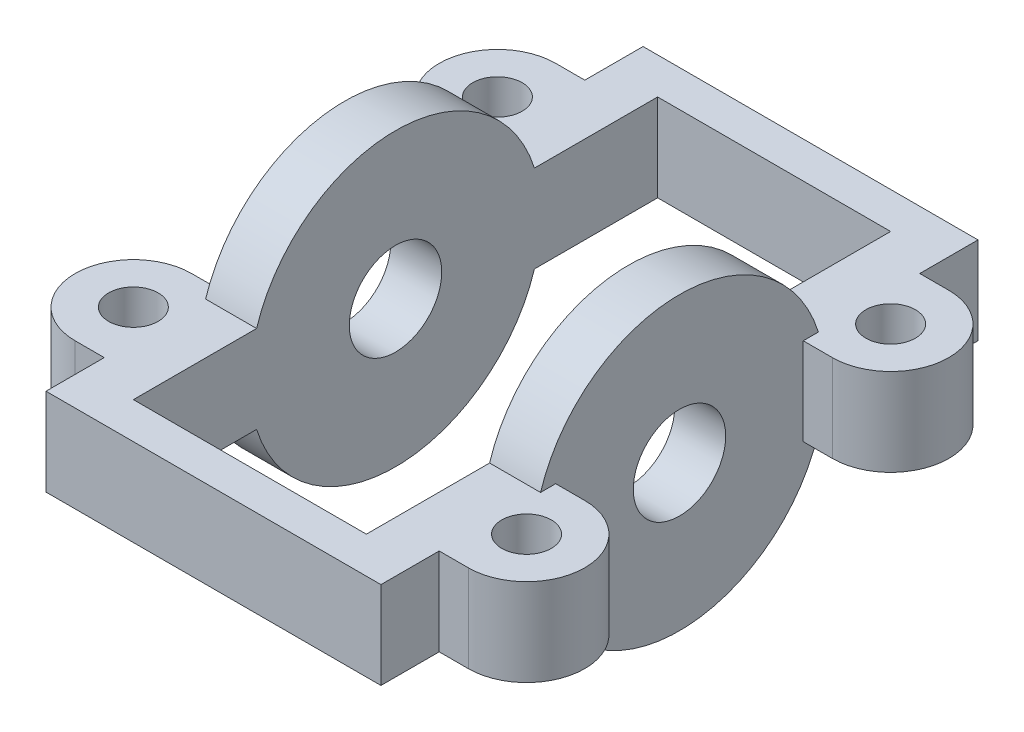
SolidWorks part; units mm, degrees
ref_plane "Front Plane" through (0, 0, 0) normal (0, 0, 1) x (1, 0, 0)
ref_plane "Top Plane" through (0, 0, 0) normal (0, 1, 0) x (1, 0, 0)
ref_plane "Right Plane" through (0, 0, 0) normal (1, 0, 0) x (0, 0, -1)
ref_plane "Ground Plane" through (0, -20.5, 0) normal (0, 1, 0) x (1, 0, 0)
sketch "Sketch1" plane through (0, 0, 0) normal (0, 1, 0) x (1, 0, 0)
  line L0 (7.5, -17.5) -> (7.5, 17.5) construction
  line L1 (-11.5, -20.5) -> (11.5, -20.5)
  line L2 (-11.5, -20.5) -> (-11.5, 20.5)
  line L3 (-11.5, 20.5) -> (11.5, 20.5)
  line L4 (11.5, -20.5) -> (11.5, 20.5)
  line L5 (-11.5, -20.5) -> (11.5, 20.5) construction
  line L6 (-11.5, 20.5) -> (11.5, -20.5) construction
  line L7 (-7.5, 17.5) -> (-7.5, -17.5) construction
  line L8 (7.5, -17.5) -> (7.5, 17.5) construction
  line L9 (-7.5, 17.5) -> (-7.5, -17.5) construction
  point P0 (0, 0)
  dimension "D1" = 4
  dimension "D2" = 3
extrude "Boss-Extrude1" add sketch "Sketch1" against normal blind 6
sketch "Sketch3" plane through (11.5, 0, 0) normal (1, 0, 0) x (0, 0, -1)
  circle A2 centre (0, -3) radius 10
  circle A3 centre (0, -3) radius 17.5 construction
  dimension "D1" = 20
extrude "Boss-Extrude2" add sketch "Sketch3" against normal up to surface (23 mm away) up to face at (-11.5, -3, 0)
sketch "Sketch4" plane through (0, 0, 0) normal (0, 1, 0) x (1, 0, 0)
  line L0 (7.5, -17.5) -> (7.5, 17.5) construction
  line L1 (-7.5, 17.5) -> (-7.5, -17.5) construction
  line L2 (7.5, -17.5) -> (7.5, 17.5) construction
  line L3 (-7.5, 17.5) -> (-7.5, -17.5) construction
  line L4 (-7.5, 17.5) -> (7.5, 17.5) construction
  line L5 (7.5, -17.5) -> (-7.5, -17.5) construction
  line L6 (8, -18) -> (8, 18)
  line L7 (-8, 18) -> (8, 18)
  line L8 (-8, 18) -> (-8, -18)
  line L9 (8, -18) -> (-8, -18)
  dimension "D1" = 0.5
extrude "Cut-Extrude1" cut sketch "Sketch4" against normal through all both and the other way through all
sketch "Sketch5" plane through (0, 0, 0) normal (1, 0, 0) x (0, 0, -1)
  circle A0 centre (0, -3) radius 3.175
  arc A1 (9.5394, 0) -> (-9.5394, 0) centre (0, -3) ccw construction
  dimension "D1" = 6.35
extrude "Cut-Extrude2" cut sketch "Sketch5" against normal through all both and the other way through all
sketch "Sketch7" plane through (0, 0, 0) normal (0, 1, 0) x (1, 0, 0)
  line L0 (11.5, 16.5) -> (13.5, 16.5)
  line L1 (13.5, 8.5) -> (11.5, 8.5)
  line L2 (11.5, 9.5394) -> (11.5, 20.5) construction
  line L3 (11.5, 8.5) -> (11.5, 16.5)
  line L4 (11.5, -16.5) -> (13.5, -16.5)
  line L5 (13.5, -8.5) -> (11.5, -8.5)
  line L6 (11.5, -20.5) -> (11.5, -9.5394) construction
  line L7 (11.5, -8.5) -> (11.5, -16.5)
  line L8 (0, 0) -> (0, 26.003) construction
  line L9 (-11.5, -8.5) -> (-11.5, -16.5)
  line L10 (-13.5, -8.5) -> (-11.5, -8.5)
  line L11 (-11.5, -16.5) -> (-13.5, -16.5)
  line L12 (-11.5, 8.5) -> (-11.5, 16.5)
  line L13 (-13.5, 8.5) -> (-11.5, 8.5)
  line L14 (-11.5, 16.5) -> (-13.5, 16.5)
  line L15 (13.5, 8.5) -> (13.5, -8.5) construction
  line L16 (0, 0) -> (13.5, 0) construction
  arc A0 (13.5, 16.5) -> (13.5, 8.5) centre (13.5, 12.5) cw
  arc A1 (13.5, -16.5) -> (13.5, -8.5) centre (13.5, -12.5) ccw
  arc A2 (-13.5, -16.5) -> (-13.5, -8.5) centre (-13.5, -12.5) cw
  arc A3 (-13.5, 16.5) -> (-13.5, 8.5) centre (-13.5, 12.5) ccw
  dimension "D1" = 8
  dimension "D2" = 2
  dimension "D3" = 17
extrude "Boss-Extrude3" add sketch "Sketch7" against normal up to surface (6 mm away) up to face at (0, -6, 14.3947)
hole_wizard "M3 Clearance Hole1" positions "Sketch8" profile "Sketch9" hole size "M3" standard "ANSI Metric" end condition through all
sketch "Sketch8" plane through (0, 0, 0) normal (0, 1, 0) x (1, 0, 0)
  point P0 (13.5, 12.5)
  point P3 (-13.5, 12.5)
  point P6 (-13.5, -12.5)
  point P9 (13.5, -12.5)
sketch "Sketch9" plane through (13.5, 0, -12.5) normal (1, 0, 0) x (0, 0, 1)
  line L0 (0, 0) -> (0, 13)
  line L1 (0, 13) -> (1.7, 13)
  line L2 (1.7, 13) -> (1.7, 0)
  line L5 (1.7, 0) -> (0, 0)
  line L11 (0, -6.35) -> (0, 107.95) construction
  dimension "Thru Hole Dia." = 3.4
  dimension "Thru Hole Depth" = 13
sketch "Sketch10" plane through (0, 0, 0) normal (0, 1, 0) x (1, 0, 0)
  line L1 (13.5, -12.5) -> (-13.5, -12.5)
  line L2 (13.5, -12.5) -> (13.5, 12.5)
  line L3 (13.5, 12.5) -> (-13.5, 12.5)
  line L4 (-13.5, -12.5) -> (-13.5, 12.5)
  line L5 (13.5, -12.5) -> (-13.5, 12.5) construction
  line L6 (13.5, 12.5) -> (-13.5, -12.5) construction
  point P0 (0, 0)
